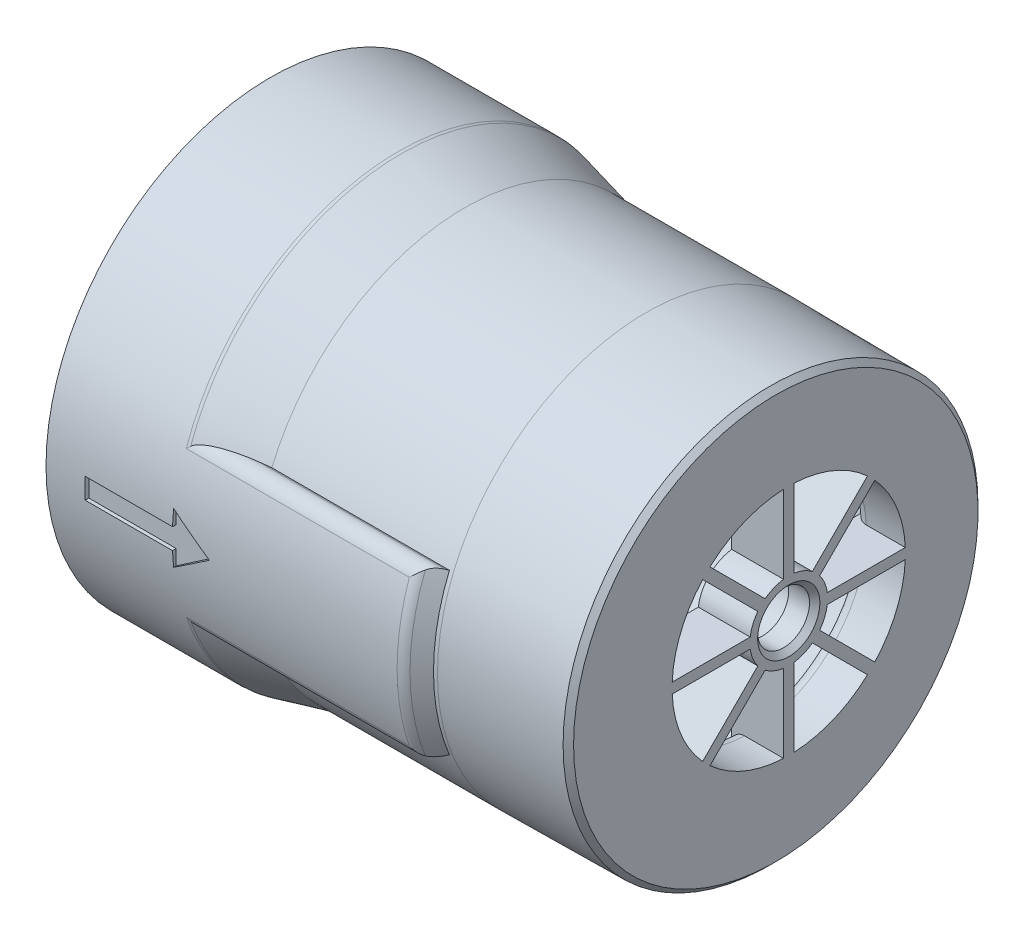
SolidWorks part; units mm, degrees
ref_plane "Front Plane" through (0, 0, 0) normal (0, 0, 1) x (1, 0, 0)
ref_plane "Top Plane" through (0, 0, 0) normal (0, 1, 0) x (1, 0, 0)
ref_plane "Right Plane" through (0, 0, 0) normal (1, 0, 0) x (0, 0, -1)
sketch "Sketch1" plane through (0, 0, 0) normal (0, 0, 1) x (1, 0, 0)
  line L0 (-80.1124, 0) -> (69.6237, 0) construction
  line L1 (-80.2087, 17.3) -> (-70.2087, 17.3)
  line L2 (-70.2087, 17.3) -> (-65.2087, 16.1)
  line L3 (-65.2087, 16.1) -> (-51.2087, 16.1)
  line L4 (-80.2087, 16.1) -> (-70.2092, 16.1)
  line L5 (-70.2092, 16.1) -> (-65.2092, 14.9)
  line L6 (-65.2092, 14.9) -> (-45.2092, 14.9)
  line L7 (-80.2087, 17.3) -> (-80.2087, 16.1)
  line L8 (-45.2092, 14.9) -> (-45.2092, 0)
  line L9 (-45.2092, 0) -> (-41.2092, 0)
  line L10 (-41.2092, 0) -> (-41.2092, 16)
  line L11 (-41.2092, 16) -> (-51.2087, 16.1)
  line L12 (-70.2087, 17.3) -> (-70.2092, 16.1) construction
  dimension "D2" = 10
  dimension "D3" = 16.1
  dimension "D4" = 10
  dimension "D5" = 14
  dimension "D6" = 5
  dimension "D7" = 16.1
  dimension "D8" = 41.2092
  dimension "D9" = 20
  dimension "D1" = 4
  dimension "D10" = 5
  dimension "D11" = 16
  dimension "D12" = 1.2
  dimension "D13" = 1.2
revolve "Revolve1" add sketch "Sketch1" angle 360 about L0
sketch "Sketch2" plane through (-41.2092, 0, 0) normal (1, 0, 0) x (0, 0, -1)
  line L0 (1, 0) -> (-21.0341, 0) construction
  line L1 (-1.9732, 0.4) -> (-4.9867, 0.4)
  line L3 (1, 0) -> (-21.0341, 0) construction
  line L10 (1, 0) -> (-16.203, 17.203) construction
  line L11 (-5.6405, 6.0748) -> (-3.516, 3.9504)
  line L12 (-4.9867, 0.4) -> (-7.9911, 0.4)
  line L13 (-3.516, 3.9504) -> (-1.3852, 1.8195)
  line L14 (0.6, 5.9867) -> (0.6, 2.9732)
  line L15 (-0.8195, 2.3852) -> (-2.9504, 4.516)
  line L16 (0.6, 8.9911) -> (0.6, 5.9867)
  line L17 (-2.9504, 4.516) -> (-5.0748, 6.6405)
  line L18 (4.9504, 4.516) -> (2.8195, 2.3852)
  line L19 (1.4, 2.9732) -> (1.4, 5.9867)
  line L20 (7.0748, 6.6405) -> (4.9504, 4.516)
  line L21 (1.4, 5.9867) -> (1.4, 8.9911)
  line L22 (6.9867, 0.4) -> (3.9732, 0.4)
  line L23 (3.3852, 1.8195) -> (5.516, 3.9504)
  line L24 (9.9911, 0.4) -> (6.9867, 0.4)
  line L25 (5.516, 3.9504) -> (7.6405, 6.0748)
  line L26 (5.516, -3.9504) -> (3.3852, -1.8195)
  line L27 (3.9732, -0.4) -> (6.9867, -0.4)
  line L28 (7.6405, -6.0748) -> (5.516, -3.9504)
  line L29 (6.9867, -0.4) -> (9.9911, -0.4)
  line L30 (1.4, -5.9867) -> (1.4, -2.9732)
  line L31 (2.8195, -2.3852) -> (4.9504, -4.516)
  line L32 (1.4, -8.9911) -> (1.4, -5.9867)
  line L33 (4.9504, -4.516) -> (7.0748, -6.6405)
  line L34 (-2.9504, -4.516) -> (-0.8195, -2.3852)
  line L35 (0.6, -2.9732) -> (0.6, -5.9867)
  line L36 (-5.0748, -6.6405) -> (-2.9504, -4.516)
  line L37 (0.6, -5.9867) -> (0.6, -8.9911)
  line L38 (-4.9867, -0.4) -> (-1.9732, -0.4)
  line L39 (-1.3852, -1.8195) -> (-3.516, -3.9504)
  line L40 (-7.9911, -0.4) -> (-4.9867, -0.4)
  line L41 (-3.516, -3.9504) -> (-5.6405, -6.0748)
  circle A9 centre (0, 0) radius 16 construction
  arc A11 (-7.9911, 0.4) -> (-5.6405, 6.0748) centre (1, 0) cw
  arc A15 (-1.9732, 0.4) -> (-1.3852, 1.8195) centre (1, 0) cw
  arc A18 (-0.8195, 2.3852) -> (0.6, 2.9732) centre (1, 0) cw
  arc A21 (-5.0748, 6.6405) -> (0.6, 8.9911) centre (1, 0) cw
  arc A22 (1.4, 2.9732) -> (2.8195, 2.3852) centre (1, 0) cw
  arc A25 (1.4, 8.9911) -> (7.0748, 6.6405) centre (1, 0) cw
  arc A26 (3.3852, 1.8195) -> (3.9732, 0.4) centre (1, 0) cw
  arc A29 (7.6405, 6.0748) -> (9.9911, 0.4) centre (1, 0) cw
  arc A30 (3.9732, -0.4) -> (3.3852, -1.8195) centre (1, 0) cw
  arc A33 (9.9911, -0.4) -> (7.6405, -6.0748) centre (1, 0) cw
  arc A34 (2.8195, -2.3852) -> (1.4, -2.9732) centre (1, 0) cw
  arc A37 (7.0748, -6.6405) -> (1.4, -8.9911) centre (1, 0) cw
  arc A38 (0.6, -2.9732) -> (-0.8195, -2.3852) centre (1, 0) cw
  arc A41 (0.6, -8.9911) -> (-5.0748, -6.6405) centre (1, 0) cw
  arc A42 (-1.3852, -1.8195) -> (-1.9732, -0.4) centre (1, 0) cw
  arc A45 (-5.6405, -6.0748) -> (-7.9911, -0.4) centre (1, 0) cw
  point P11 (1, 0)
  point P27 (2, 0)
  point P74 (1, 0)
  dimension "D2" = 0.4
  dimension "D4" = 9
  dimension "D8" = 3
  dimension "D9" = 8
  dimension "D1" = 45
  dimension "D3" = 0.4
  dimension "D5" = 1
ref_plane "Plane1" through (0, 0, 12) normal (0, 0, 1) x (1, 0, 0)
extrude "Cut-Extrude5" cut sketch "Sketch2" against normal up to next
ref_plane "Plane3" through (0, 0, -1) normal (0, 0, -1) x (-1, 0, 0)
sketch "Sketch8" plane through (0, 0, -1) normal (0, 0, -1) x (-1, 0, 0)
  line L0 (41.4715, 0) -> (64.2594, 0) construction
  line L1 (45.2092, -2.5) -> (43.2092, -2.5)
  line L2 (41.2092, 16) -> (41.2092, -16) construction
  line L3 (45.2092, -2.5) -> (45.2092, 0)
  line L4 (41.2092, -2) -> (41.2092, 0)
  line L5 (45.2092, 0) -> (41.2092, 0)
  line L6 (43.2092, -2.5) -> (43.2092, -2)
  line L7 (43.2092, -2) -> (41.2092, -2)
  dimension "D1" = 2.5
  dimension "D2" = 2
  dimension "D3" = 4
  dimension "D4" = 2
revolve "Cut-Revolve2" cut sketch "Sketch8" angle 360 about L0
chamfer "Chamfer1" distance 0.4 angle 45 3 edges at (-41.2092, 0, 16) (-80.2087, 0, 16.1) (-41.2092, 0, -3) first distance on face at (-41.2092, 0, -3) first distance on face at (-80.2087, 0, 16.1)
fillet "Fillet10" radius 1 8 edges at (-45.2092, 3.4442, 7.3149) (-45.2092, 8.3149, 2.4442) (-45.2092, 8.3149, -4.4442) (-45.2092, 3.4442, -9.3149) (-45.2092, -3.4442, -9.3149) (-45.2092, -8.3149, -4.4442) (-45.2092, -8.3149, 2.4442) (-45.2092, -3.4442, 7.3149)
fillet "Fillet4" radius 10 1 edges at (-70.2092, 0, 16.1)
sketch "Sketch12" plane through (0, 0, 0) normal (0, 1, 0) x (1, 0, 0)
  line L0 (-38.7859, 0) -> (-87.7556, 0) construction
  line L1 (-51.5117, -16.103) -> (-65.2087, -16.1)
  line L3 (-70.2087, -17.3) -> (-52.7087, -17.3)
  line L4 (-70.2092, 17.2) -> (-65.2092, 16)
  line L5 (-65.2087, -16.1) -> (-70.2087, -17.3)
  line L6 (-65.2087, -16.1) -> (-70.2087, -17.3)
  line L7 (-52.7087, -17.3) -> (-51.5117, -16.103)
  line L8 (-65.2092, 16) -> (-41.2092, 16)
  line L9 (-41.6132, -16.004) -> (-51.2087, -16.1)
  line L10 (-41.6132, -16.004) -> (-51.2087, -16.1) construction
  dimension "D1" = 17.5
  dimension "D2" = 45
revolve "Revolve2" add sketch "Sketch12" angle 45 mid plane about L0 region at (-59.976, 0, 16.7251)
ref_plane "Plane4" through (0, 0, 17) normal (0, 0, 1) x (1, 0, 0)
sketch "Sketch13" plane through (0, 0, 17) normal (0, 0, 1) x (1, 0, 0)
  line L0 (-77.1995, 0.799) -> (-70.4645, 0.799)
  line L1 (-70.4645, 1.958) -> (-70.4645, 0.799)
  line L2 (-70.4645, 1.958) -> (-67.6061, 0)
  line L3 (-77.1995, 0.799) -> (-77.1995, -0.799)
  line L4 (-66.0568, 0) -> (-78.8911, 0) construction
  line L5 (-77.1995, -0.799) -> (-70.4645, -0.799)
  line L6 (-70.4645, -1.958) -> (-70.4645, -0.799)
  line L7 (-70.4645, -1.958) -> (-67.6061, 0)
  point P10 (-77.1995, 0)
extrude "Cut-Extrude6" cut sketch "Sketch13" along normal blind 1.2
fillet "Fillet7" radius 1 4 edges at (-61.4587, 6.6204, 15.9831) (-52.7087, 0, 17.3) (-61.4587, -6.6204, 15.9831) (-70.2087, 0, -17.3)
